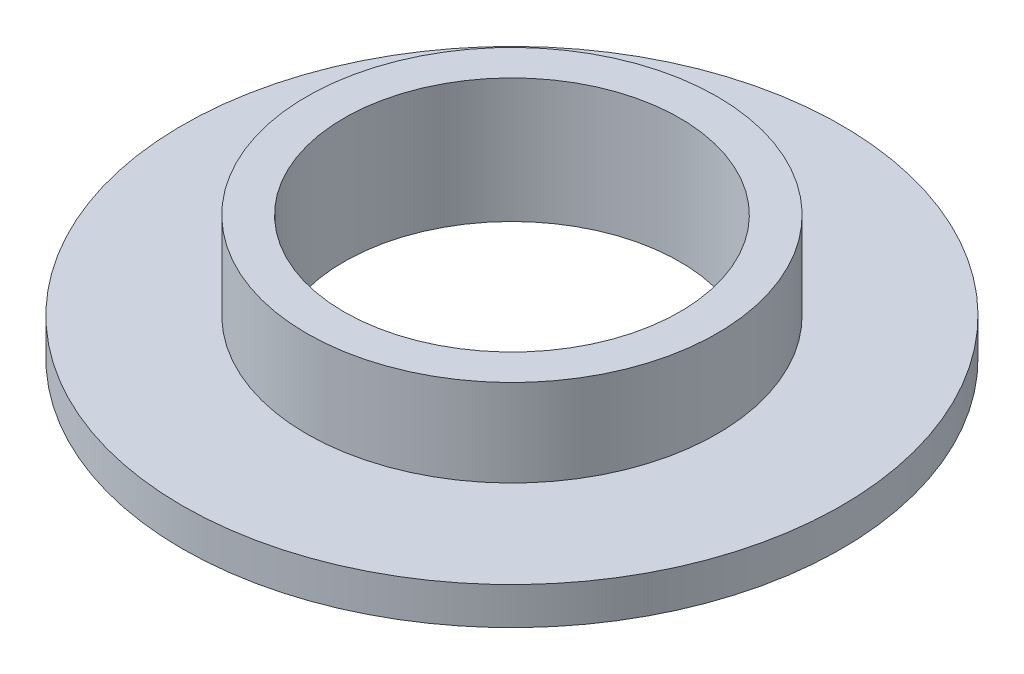
SolidWorks part; units mm, degrees
ref_plane "Front Plane" through (0, 0, 0) normal (0, 0, 1) x (1, 0, 0)
ref_plane "Top Plane" through (0, 0, 0) normal (0, 1, 0) x (1, 0, 0)
ref_plane "Right Plane" through (0, 0, 0) normal (1, 0, 0) x (0, 0, -1)
sketch "Sketch1" plane through (0, 0, 0) normal (0, 1, 0) x (1, 0, 0)
  circle A0 centre (0, 0) radius 13.5
  circle A1 centre (0, 0) radius 16.5
  circle A2 centre (0, 0) radius 26.5
  dimension "D1" = 27
  dimension "D2" = 3
  dimension "D3" = 10
extrude "Boss-Extrude1" add sketch "Sketch1" along normal blind 10 contours A1 A0 region at (-16.0333, 0, 0)
extrude "Boss-Extrude2" add sketch "Sketch1<3>" along normal blind 3 contours A2 A1 region at (-25.7505, 0, 0)
sketch "Sketch1<3>" plane through (0, 0, 0) normal (0, 1, 0) x (1, 0, 0) same geometry as "Sketch1"
